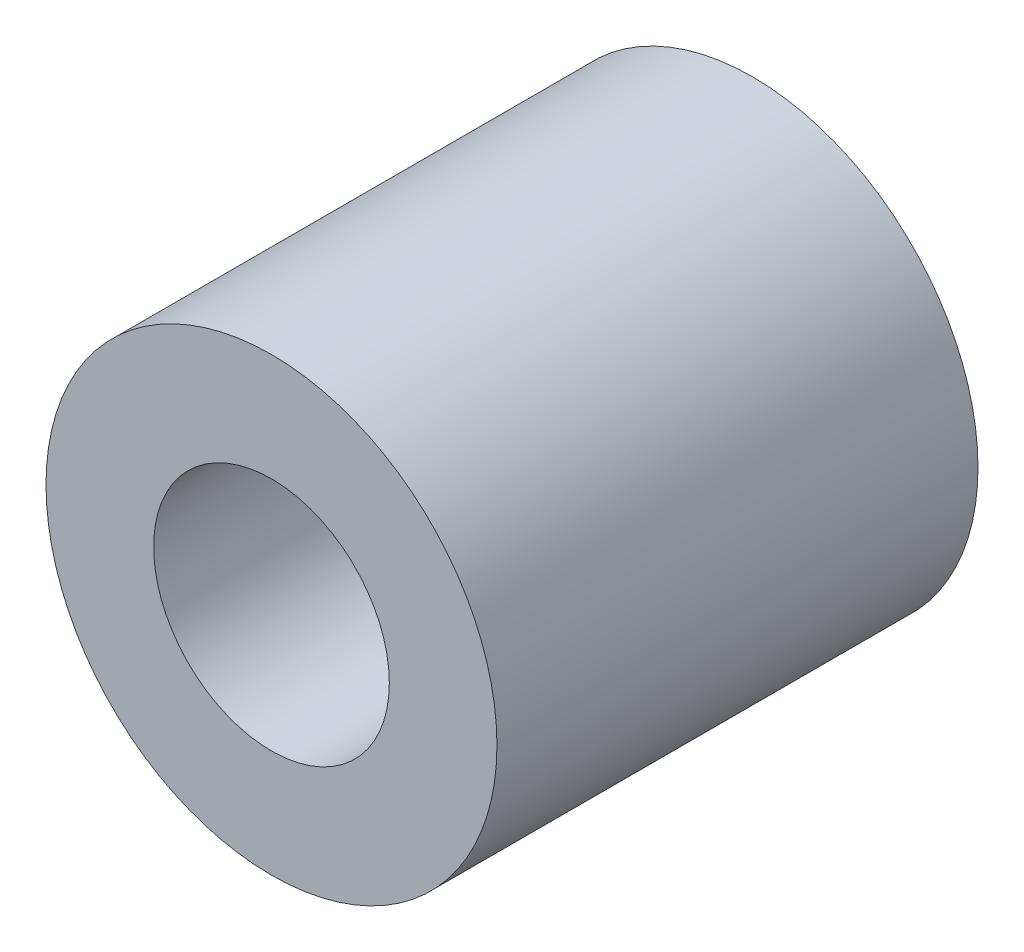
SolidWorks part; units mm, degrees
material "6061-T6 (SS)"
ref_plane "Front Plane" through (0, 0, 0) normal (0, 0, 1) x (1, 0, 0)
ref_plane "Top Plane" through (0, 0, 0) normal (0, 1, 0) x (1, 0, 0)
ref_plane "Right Plane" through (0, 0, 0) normal (1, 0, 0) x (0, 0, -1)
sketch "Sketch1" plane through (0, 0, 0) normal (0, 0, 1) x (1, 0, 0)
  circle A0 centre (0, 0) radius 2.4892
  circle A1 centre (0, 0) radius 4.7625
  dimension "D1" = 4.9784
  dimension "D2" = 9.525
extrude "Boss-Extrude1" add sketch "Sketch1" along normal blind 10.16
